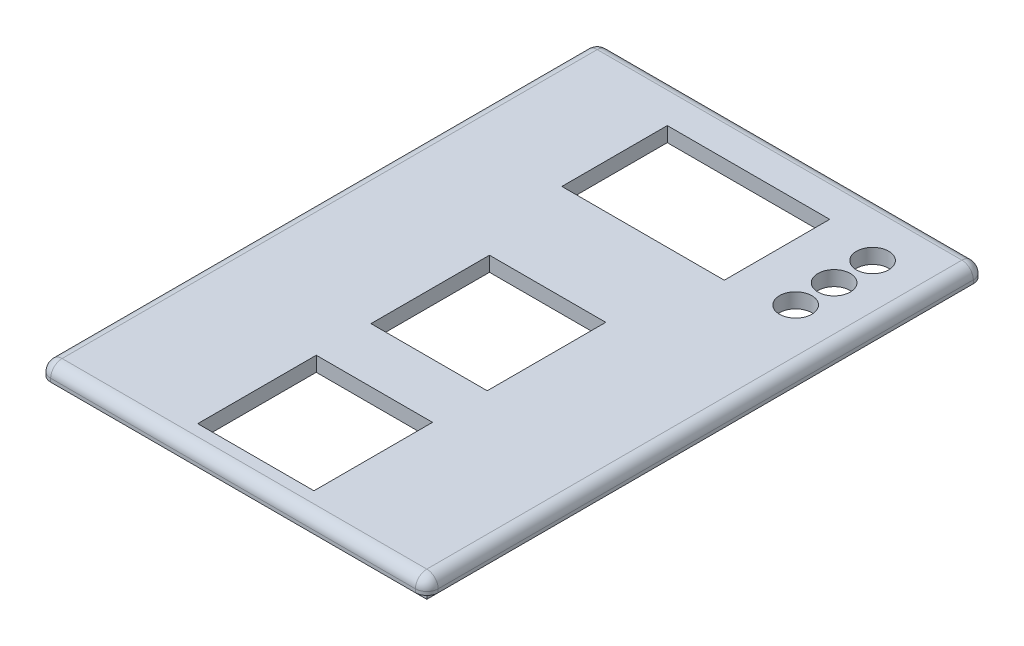
SolidWorks part; units mm, degrees
material "ABS"
ref_plane "Front Plane" through (0, 0, 0) normal (0, 0, 1) x (1, 0, 0)
ref_plane "Top Plane" through (0, 0, 0) normal (0, 1, 0) x (1, 0, 0)
ref_plane "Right Plane" through (0, 0, 0) normal (1, 0, 0) x (0, 0, -1)
sketch "Sketch1" plane through (0, 0, 0) normal (0, 1, 0) x (1, 0, 0)
  line L1 (0, 0) -> (86.36, 0)
  line L2 (0, 0) -> (0, 124.333)
  line L3 (0, 124.333) -> (86.36, 124.333)
  line L4 (86.36, 0) -> (86.36, 124.333)
extrude "Boss-Extrude1" add sketch "Sketch1" along normal blind 3.302
sketch "Sketch2" plane through (0, 0, 0) normal (0, -1, 0) x (1, 0, 0)
  line L1 (2.54, -2.54) -> (83.82, -2.54)
  line L2 (2.54, -2.54) -> (2.54, -121.793)
  line L3 (2.54, -121.793) -> (83.82, -121.793)
  line L4 (83.82, -2.54) -> (83.82, -121.793)
extrude "Boss-Extrude2" add sketch "Sketch2" along normal blind 2.54
sketch "Sketch4" plane through (0, -2.54, 0) normal (0, -1, 0) x (1, 0, 0)
  line L2 (2.54, -121.793) -> (83.82, -121.793) construction
  line L3 (58.42, -121.793) -> (58.42, -119.253)
  line L4 (81.28, -119.253) -> (81.28, -5.08)
  line L5 (58.42, -119.253) -> (81.28, -119.253)
  line L6 (5.08, -119.253) -> (5.08, -5.08)
  line L7 (27.94, -121.793) -> (58.42, -121.793)
  line L8 (81.28, -5.08) -> (58.42, -5.08)
  line L9 (27.94, -2.54) -> (58.42, -2.54)
  line L10 (58.42, -5.08) -> (58.42, -2.54)
  line L11 (83.82, -2.54) -> (2.54, -2.54) construction
  line L12 (27.94, -2.54) -> (27.94, -5.08)
  line L13 (27.94, -5.08) -> (5.08, -5.08)
  line L14 (5.08, -119.253) -> (27.94, -119.253)
  line L15 (27.94, -119.253) -> (27.94, -121.793)
extrude "Cut-Extrude1" cut sketch "Sketch4" against normal blind 2.54
sketch "Sketch6" plane through (0, 3.302, 0) normal (0, 1, 0) x (1, 0, 0)
  line L1 (30.226, 5.08) -> (56.134, 5.08)
  line L2 (30.226, 5.08) -> (30.226, 31.496)
  line L3 (30.226, 31.496) -> (56.134, 31.496)
  line L4 (56.134, 5.08) -> (56.134, 31.496)
  line L5 (30.226, 43.688) -> (56.134, 43.688)
  line L6 (30.226, 43.688) -> (30.226, 70.104)
  line L7 (30.226, 70.104) -> (56.134, 70.104)
  line L8 (56.134, 43.688) -> (56.134, 70.104)
  line L9 (25.019, 114.935) -> (61.214, 114.935)
  line L10 (25.019, 114.935) -> (25.019, 91.44)
  line L11 (25.019, 91.44) -> (61.214, 91.44)
  line L12 (61.214, 114.935) -> (61.214, 91.44)
extrude "Cut-Extrude2" cut sketch "Sketch6" against normal blind 3.302
fillet "Fillet1" radius 2.54 8 edges at (86.36, 3.302, -62.1665) (43.18, 3.302, 0) (43.18, 3.302, -124.333) (0, 3.302, -62.1665) (0, 1.651, -124.333) (0, 1.651, 0) (86.36, 1.651, 0) (86.36, 1.651, -124.333)
sketch "Sketch7" plane through (0, 3.302, 0) normal (0, 1, 0) x (1, 0, 0)
  circle A0 centre (73.9429, 111.76) radius 3.6
  circle A1 centre (73.9429, 103.1875) radius 3.6
  circle A2 centre (73.9429, 94.615) radius 3.6
extrude "Cut-Extrude3" cut sketch "Sketch7" against normal through all
